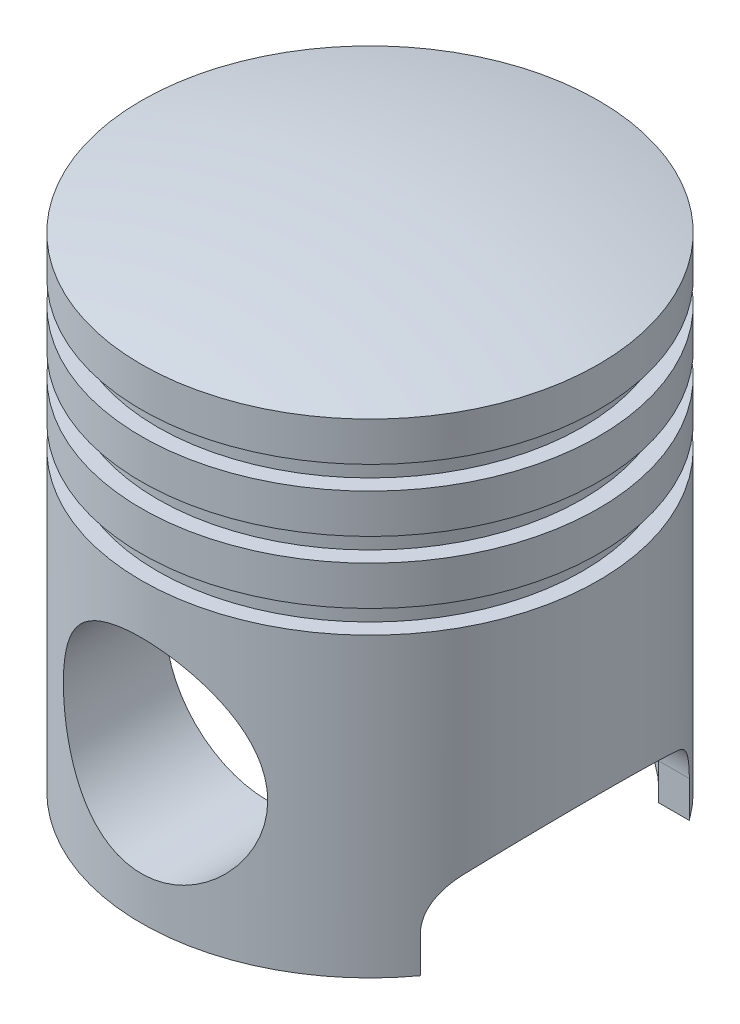
SolidWorks part; units mm, degrees
ref_plane "Front Plane" through (0, 0, 0) normal (0, 0, 1) x (1, 0, 0)
ref_plane "Top Plane" through (0, 0, 0) normal (0, 1, 0) x (1, 0, 0)
ref_plane "Right Plane" through (0, 0, 0) normal (1, 0, 0) x (0, 0, -1)
sketch "Sketch1" plane through (0, 0, 0) normal (0, 1, 0) x (1, 0, 0)
  circle A0 centre (0, 0) radius 42.5
  dimension "D1" = 85
extrude "Boss-Extrude1" add sketch "Sketch1" along normal blind 90
sketch "Sketch2" plane through (0, 90, 0) normal (0, 1, 0) x (1, 0, 0)
  circle A0 centre (0, 0) radius 39.5
  dimension "D1" = 79
extrude "Cut-Extrude2" cut sketch "Sketch2" against normal blind 4.3 from offset 7.3 flip side to cut offset against normal yes
pattern_linear "LPattern1" count 3 spacing 11.6 along (0, -1, 0) of "Cut-Extrude2"
sketch "Sketch3" plane through (0, 0, 0) normal (0, -1, 0) x (1, 0, 0)
  circle A0 centre (0, 0) radius 38
  dimension "D1" = 76
extrude "Cut-Extrude3" cut sketch "Sketch3" against normal blind 85
dome "Dome1" faces to dome 1 distance 5 reverse direction no elliptical dome no face at (0, 90, 42.5) parameters "D1"=5
sketch "Sketch4" plane through (0, 0, 0) normal (0, 0, 1) x (1, 0, 0)
  circle A0 centre (0, 27) radius 19
  dimension "D1" = 38
  dimension "D2" = 27
extrude "Cut-Extrude4" cut sketch "Sketch4" against normal through all both and the other way through all
sketch "Sketch5" plane through (0, 0, 0) normal (1, 0, 0) x (0, 0, -1)
  line L0 (0, 0) -> (0, 33.7627) construction
  line L1 (-25, 0) -> (-25, 12)
  line L2 (-42.5, 0) -> (42.5, 0) construction
  line L3 (25, 0) -> (25, 12)
  arc A0 (-25, 12) -> (25, 12) centre (0, -19.225) cw
  dimension "D3" = 40
  dimension "D1" = 12
  dimension "D2" = 50
extrude "Cut-Extrude5" cut sketch "Sketch5" against normal through all both and the other way through all
fillet "Fillet1" radius 10 4 edges at (-31.4937, 12, 25) (31.4937, 12, 25) (-31.4937, 12, -25) (31.4937, 12, -25)
sketch "Sketch7" plane through (0, 0, 0) normal (0, 0, 1) x (1, 0, 0)
  circle A0 centre (0, 27) radius 19 construction
  circle A1 centre (0, 27) radius 19
  circle A2 centre (0, 27) radius 22.5
  dimension "D1" = 45
extrude "Boss-Extrude2" add sketch "Sketch7" along normal up to next from offset 19
mirror "Mirror1" about plane through (0, 0, 0) normal (0, 0, 1) of "Boss-Extrude2"
